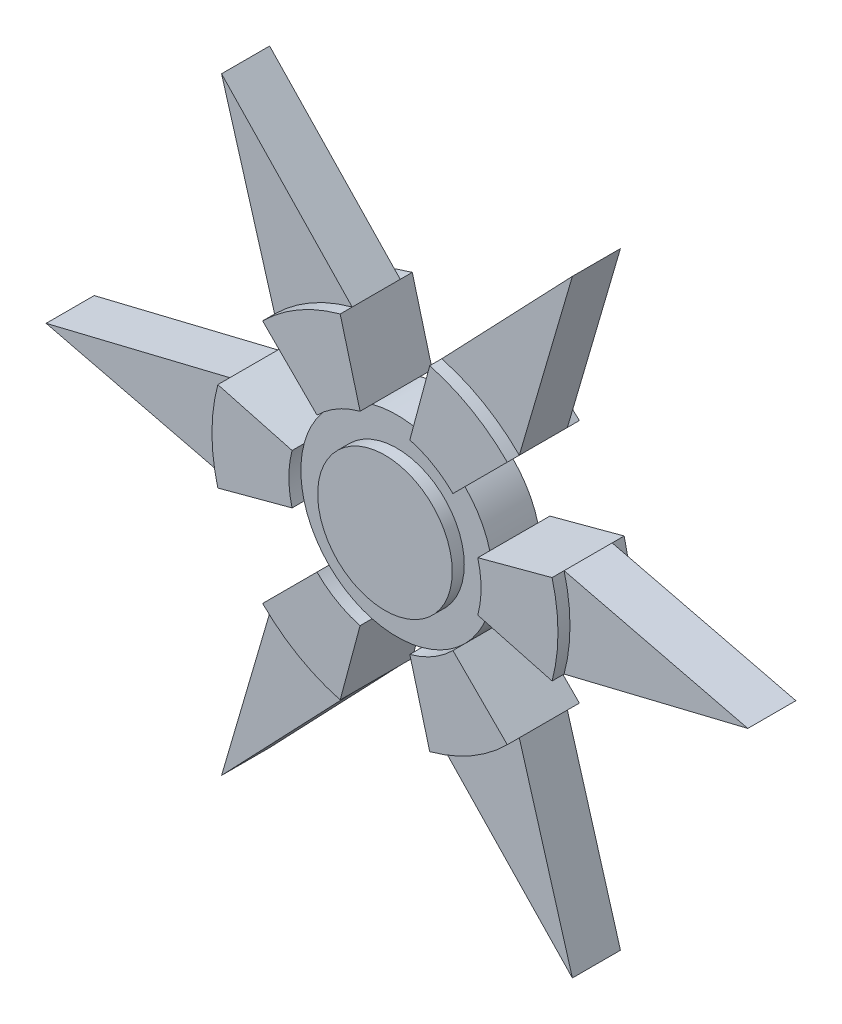
SolidWorks part; units mm, degrees
material "Pine"
ref_plane "Front Plane" through (0, 0, 0) normal (0, 0, 1) x (1, 0, 0)
ref_plane "Top Plane" through (0, 0, 0) normal (0, 1, 0) x (1, 0, 0)
ref_plane "Right Plane" through (0, 0, 0) normal (1, 0, 0) x (0, 0, -1)
sketch "Sketch1" plane through (0, 0, 0) normal (0, 0, 1) x (1, 0, 0)
  line L0 (0, 0) -> (50000, 0) construction
  line L1 (34.7733, 9.3175) -> (19.3185, 5.1764)
  line L2 (34.7733, -9.3175) -> (19.3185, -5.1764)
  line L3 (34.7733, 9.3175) -> (73, 0)
  line L4 (34.7733, -9.3175) -> (73, 0)
  line L5 (25.4558, -25.4558) -> (36.5, -63.2199)
  line L6 (9.3175, -34.7733) -> (36.5, -63.2199)
  line L7 (25.4558, -25.4558) -> (14.1421, -14.1421)
  line L8 (9.3175, -34.7733) -> (5.1764, -19.3185)
  line L9 (-9.3175, -34.7733) -> (-36.5, -63.2199)
  line L10 (-25.4558, -25.4558) -> (-36.5, -63.2199)
  line L11 (-9.3175, -34.7733) -> (-5.1764, -19.3185)
  line L12 (-25.4558, -25.4558) -> (-14.1421, -14.1421)
  line L13 (-34.7733, -9.3175) -> (-73, 0)
  line L14 (-34.7733, 9.3175) -> (-73, 0)
  line L15 (-34.7733, -9.3175) -> (-19.3185, -5.1764)
  line L16 (-34.7733, 9.3175) -> (-19.3185, 5.1764)
  line L17 (-25.4558, 25.4558) -> (-36.5, 63.2199)
  line L18 (-9.3175, 34.7733) -> (-36.5, 63.2199)
  line L19 (-25.4558, 25.4558) -> (-14.1421, 14.1421)
  line L20 (-9.3175, 34.7733) -> (-5.1764, 19.3185)
  line L21 (9.3175, 34.7733) -> (36.5, 63.2199)
  line L22 (25.4558, 25.4558) -> (36.5, 63.2199)
  line L23 (9.3175, 34.7733) -> (5.1764, 19.3185)
  line L24 (25.4558, 25.4558) -> (14.1421, 14.1421)
  circle A0 centre (0, 0) radius 20
  circle A1 centre (0, 0) radius 14
  arc A2 (25.4558, 25.4558) -> (9.3175, 34.7733) centre (0, 0) ccw
  circle A4 centre (0, 0) radius 73 construction
  arc A5 (25.4558, 25.4558) -> (9.3175, 34.7733) centre (0, 0) ccw
  arc A6 (34.7733, -9.3175) -> (34.427, 10.5254) centre (0, 0) ccw
  arc A7 (34.7733, -9.3175) -> (34.427, 10.5254) centre (0, 0) ccw
  arc A8 (9.3175, -34.7733) -> (25.4558, -25.4558) centre (0, 0) ccw
  arc A9 (9.3175, -34.7733) -> (25.4558, -25.4558) centre (0, 0) ccw
  arc A10 (-25.4558, -25.4558) -> (-9.3175, -34.7733) centre (0, 0) ccw
  arc A11 (-25.4558, -25.4558) -> (-9.3175, -34.7733) centre (0, 0) ccw
  arc A12 (-34.7733, 9.3175) -> (-34.7733, -9.3175) centre (0, 0) ccw
  arc A13 (-34.7733, 9.3175) -> (-34.7733, -9.3175) centre (0, 0) ccw
  arc A14 (-9.3175, 34.7733) -> (-25.4558, 25.4558) centre (0, 0) ccw
  arc A15 (-9.3175, 34.7733) -> (-25.4558, 25.4558) centre (0, 0) ccw
  point P41 (0, 0)
  dimension "D1" = 40
  dimension "D2" = 28
  dimension "D3" = 72
  dimension "D5" = 146
  dimension "D7" = 72
  dimension "D4" = 30
  dimension "D6" = 6
extrude "Boss-Extrude1" add sketch "Sketch1" along normal mid plane 15 contours A1 | L24 A2 L23 A0 | L2 A6 L1 A0 | L8 A8 L7 A0 | L12 A10 L11 A0 | L16 A12 L15 A0 | L20 A14 L19 A0 region at (28.4345, 0, 0) region at (14.2172, 24.625, 0) region at (14.2172, -24.625, 0) region at (-14.2172, 24.625, 0) region at (-14.2172, -24.625, 0) region at (-28.4345, 0, 0) region at (0, 0, 0)
extrude "Boss-Extrude3" add sketch "Sketch1<6>" along normal mid plane 10 contours A2 L22 L21 | A14 L18 L17 | A12 L14 L13 | A10 L10 L9 | A8 L6 L5 | A6 L4 L3 | A0 A1 region at (48.0651, 0, 0) region at (19.2681, 2.5367, 0) region at (24.0326, 41.6256, 0) region at (24.0326, -41.6256, 0) region at (-24.0326, 41.6256, 0) region at (-24.0326, -41.6256, 0) region at (-48.0651, 0, 0)
sketch "Sketch1<6>" plane through (0, 0, 0) normal (0, 0, 1) x (1, 0, 0) same geometry as "Sketch1"
